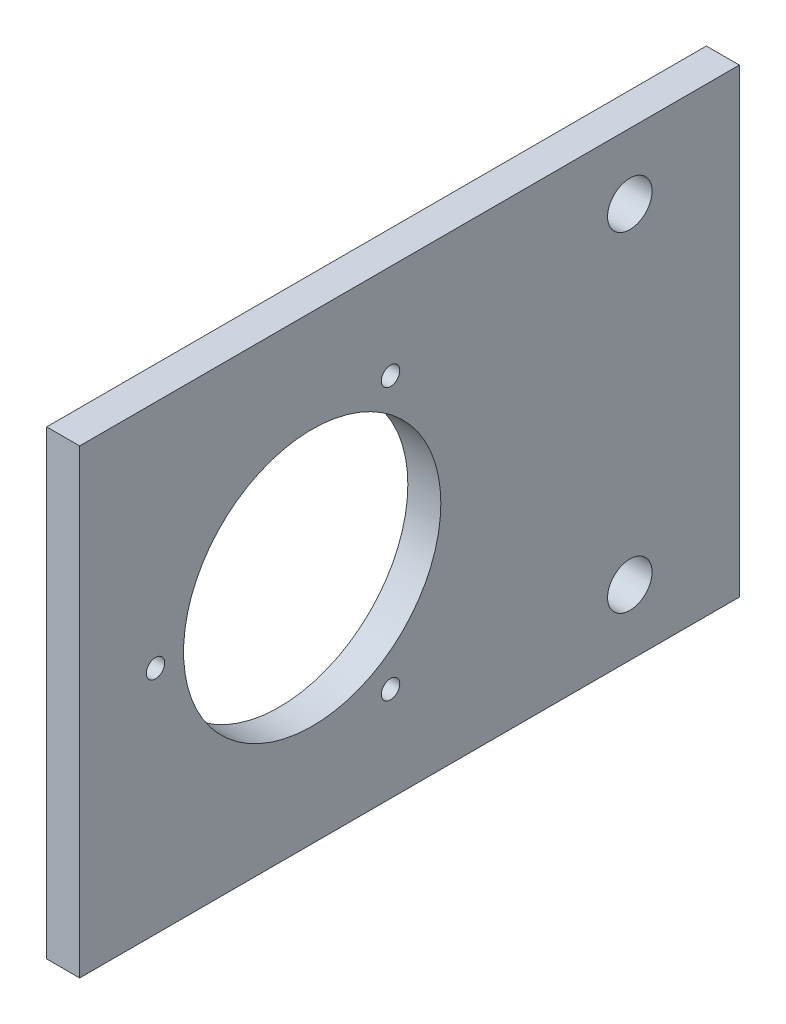
SolidWorks part; units mm, degrees
ref_plane "Front Plane" through (0, 0, 0) normal (1, 0, 0) x (0, 1, 0)
ref_plane "Top Plane" through (0, 0, 0) normal (0, 0, 1) x (0, 1, 0)
ref_plane "Right Plane" through (0, 0, 0) normal (0, 1, 0) x (-1, 0, 0)
sketch "Sketch1" plane through (0, 0, 0) normal (1, 0, 0) x (0, 1, 0)
  line L0 (-34.925, 14.75) -> (34.925, 14.75) construction
  line L1 (-34.925, -50) -> (34.925, -50)
  line L2 (-34.925, -50) -> (-34.925, 50)
  line L3 (-34.925, 50) -> (34.925, 50)
  line L4 (34.925, -50) -> (34.925, 50)
  line L5 (-34.925, -50) -> (34.925, 50) construction
  line L6 (-34.925, 50) -> (34.925, -50) construction
  line L7 (0, 50) -> (0, -50) construction
  line L8 (-34.925, -33.4) -> (34.925, -33.4) construction
  line L9 (0, 14.75) -> (0, 38.5) construction
  line L10 (20.5681, 2.875) -> (0, 14.75) construction
  line L11 (0, 14.75) -> (-20.5681, 2.875) construction
  circle A5 centre (0, 14.75) radius 19.5
  circle A6 centre (-25, -33.4) radius 3.3731
  circle A7 centre (25, -33.4) radius 3.3731
  circle A8 centre (-20.5681, 2.875) radius 1.4
  circle A9 centre (20.5681, 2.875) radius 1.4
  circle A10 centre (0, 38.5) radius 1.4
  point P0 (0, 0)
  dimension "D5" = 2.8
  dimension "D4" = 23.75
  dimension "D6" = 120
  dimension "D8" = 39
  dimension "D10" = 6.7462
  dimension "D1" = 100
  dimension "D2" = 69.85
  dimension "D3" = 64.75
  dimension "D7" = 120
  dimension "D9" = 16.6
  dimension "D11" = 25
extrude "Boss-Extrude1" add sketch "Sketch1" along normal blind 5
